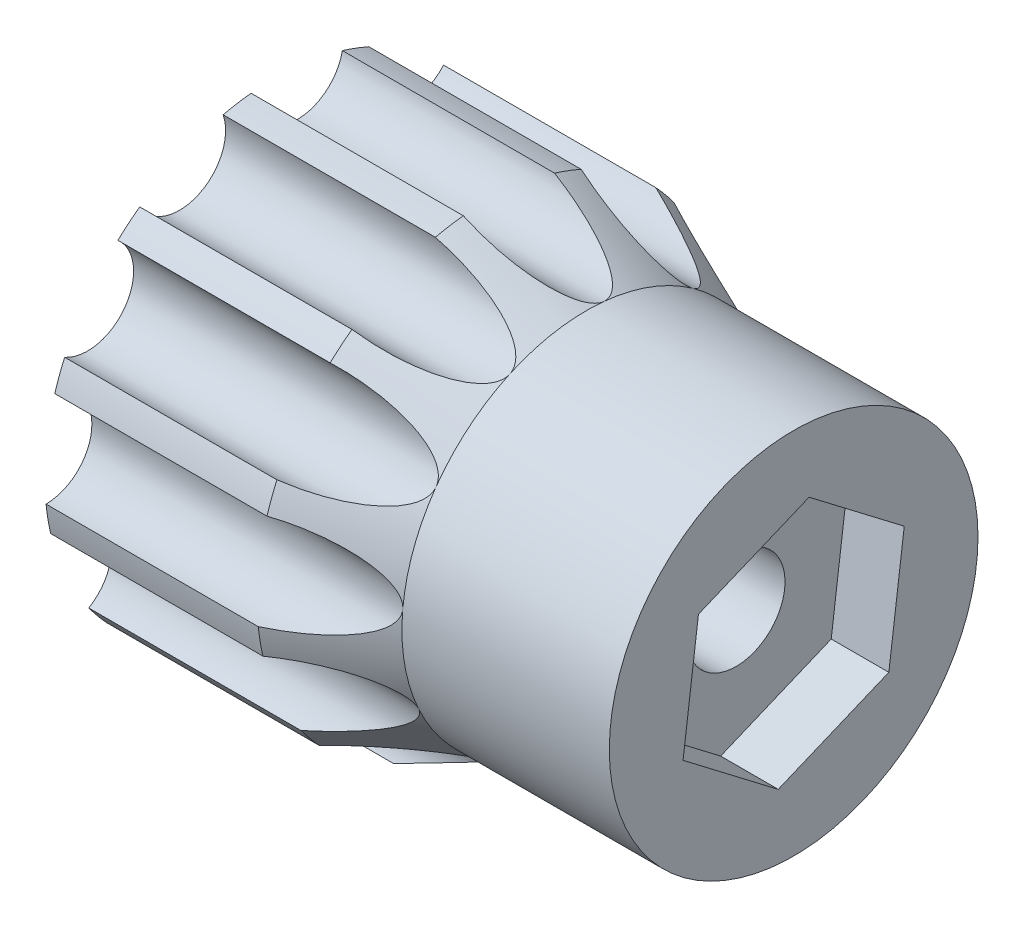
SolidWorks part; units mm, degrees
ref_plane "Front Plane" through (0, 0, 0) normal (0, 0, 1) x (1, 0, 0)
ref_plane "Top Plane" through (0, 0, 0) normal (0, 1, 0) x (1, 0, 0)
ref_plane "Right Plane" through (0, 0, 0) normal (1, 0, 0) x (0, 0, -1)
sketch "Sketch1" plane through (195.5543, 0, 0) normal (-1, 0, 0) x (0, 0, 1)
  circle A0 centre (-30.5454, -8.5722) radius 8
extrude "Boss-Extrude1" add sketch "Sketch1" along normal blind 25
sketch "Sketch2" plane through (195.5543, 0, 0) normal (1, 0, 0) x (0, 0, -1)
  line L1 (88.4638, -29.9846) -> (78.0483, 30.8803)
  line L2 (78.0483, 30.8803) -> (20.1299, 52.2927)
  line L3 (20.1299, 52.2927) -> (-27.3729, 12.8402)
  line L4 (-27.3729, 12.8402) -> (-16.9574, -48.0248)
  line L5 (-16.9574, -48.0248) -> (40.9609, -69.4372)
  line L6 (40.9609, -69.4372) -> (88.4638, -29.9846)
  circle A0 centre (30.5454, -8.5722) radius 53.4768 construction
extrude "Cut-Extrude1" cut sketch "Sketch2" against normal blind 2.5
sketch "Sketch3" plane through (170.5543, 0, 0) normal (-1, 0, 0) x (0, 0, 1)
  circle A0 centre (-30.5454, -8.5722) radius 10
extrude "Boss-Extrude2" add sketch "Sketch3" against normal blind 13.5
chamfer "Chamfer1" distance 2 angle 65 1 edges at (184.0543, -8.5722, -20.5454) first distance on face at (184.0543, -8.5722, -22.5454)
sketch "Sketch4" plane through (170.5543, 0, 0) normal (-1, 0, 0) x (0, 0, 1)
  circle A0 centre (-20.591, -7.6184) radius 2
  circle A1 centre (-30.5454, -8.5722) radius 10 construction
  circle A5 centre (-21.4478, -12.7234) radius 2
  circle A6 centre (-24.7422, -16.7161) radius 2
  circle A7 centre (-29.5916, -18.5266) radius 2
  circle A8 centre (-34.6966, -17.6699) radius 2
  circle A9 centre (-38.6893, -14.3754) radius 2
  circle A10 centre (-40.4998, -9.526) radius 2
  circle A11 centre (-39.6431, -4.421) radius 2
  circle A12 centre (-36.3486, -0.4283) radius 2
  circle A13 centre (-31.4992, 1.3822) radius 2
  circle A14 centre (-26.3942, 0.5254) radius 2
  circle A15 centre (-22.4015, -2.769) radius 2
  point P4 (0, 0)
  point P5 (-26.492, -8.7415)
  point P6 (-26.492, -8.7415)
  point P29 (-30.5454, -8.5722)
  point P31 (-26.492, -8.7415)
  dimension "D1" = 12
extrude "Cut-Extrude2" cut sketch "Sketch4" against normal blind 13.5
sketch "Sketch5" plane through (170.5543, 0, 0) normal (-1, 0, 0) x (0, 0, 1)
  circle A0 centre (-30.5454, -8.5722) radius 2.125
extrude "Cut-Extrude3" cut sketch "Sketch5" against normal blind 26.5
sketch "Sketch6" plane through (170.5543, 0, 0) normal (-1, 0, 0) x (0, 0, 1)
  circle A0 centre (-30.5454, -8.5722) radius 5.3
extrude "Cut-Extrude4" cut sketch "Sketch6" against normal blind 16.5
sketch "Sketch7" plane through (193.0543, 0, 0) normal (1, 0, 0) x (0, 0, -1)
  line L1 (35.3445, -6.5728) -> (31.2134, -3.4164)
  line L2 (31.2134, -3.4164) -> (26.4143, -5.4159)
  line L3 (26.4143, -5.4159) -> (25.7464, -10.5717)
  line L4 (25.7464, -10.5717) -> (29.8775, -13.728)
  line L5 (29.8775, -13.728) -> (34.6765, -11.7286)
  line L6 (34.6765, -11.7286) -> (35.3445, -6.5728)
  circle A0 centre (30.5454, -8.5722) radius 4.5024 construction
extrude "Cut-Extrude5" cut sketch "Sketch7" against normal blind 2.5
